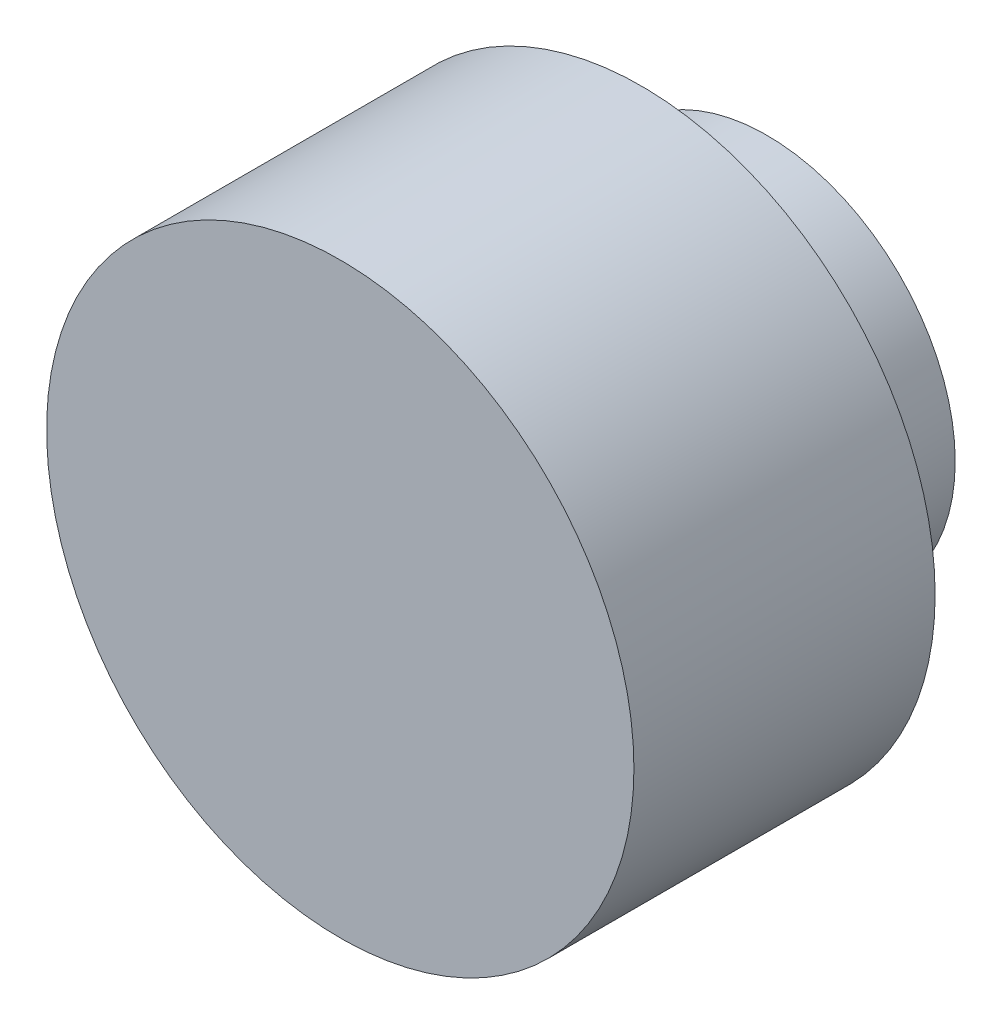
SolidWorks part; units mm, degrees
ref_plane "Front Plane" through (0, 0, 0) normal (0, 0, 1) x (1, 0, 0)
ref_plane "Top Plane" through (0, 0, 0) normal (0, 1, 0) x (1, 0, 0)
ref_plane "Right Plane" through (0, 0, 0) normal (1, 0, 0) x (0, 0, -1)
sketch "Sketch1" plane through (0, 0, 0) normal (0, 0, 1) x (1, 0, 0)
  circle A0 centre (73.892, 7.9182) radius 2.925
  circle A1 centre (73.892, 7.9182) radius 2.925 construction
  circle A7 centre (73.892, 7.9182) radius 1.875
  point P2 (0, 0)
  dimension "D1" = 3.75
extrude "Boss-Extrude1" add sketch "Sketch1" along normal blind 3 contours A0 | A7 region at (71.0497, 7.9182, 0) region at (73.892, 7.9182, 0)
extrude "Boss-Extrude2" add sketch "Sketch1<3>" against normal blind 1.25 contours A7 region at (73.892, 7.9182, 0)
sketch "Sketch1<3>" plane through (0, 0, 0) normal (0, 0, 1) x (1, 0, 0) same geometry as "Sketch1"
